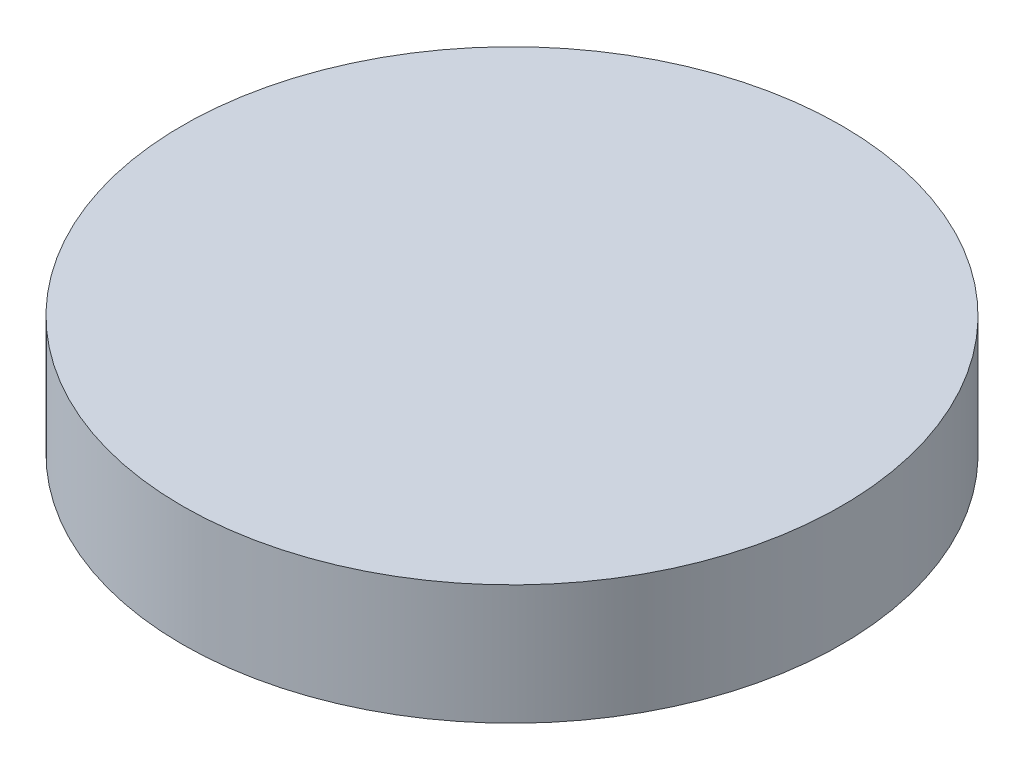
SolidWorks part; units mm, degrees
ref_plane "Front Plane" through (0, 0, 0) normal (0, 0, 1) x (1, 0, 0)
ref_plane "Top Plane" through (0, 0, 0) normal (0, 1, 0) x (1, 0, 0)
ref_plane "Right Plane" through (0, 0, 0) normal (1, 0, 0) x (0, 0, -1)
sketch "Sketch1" plane through (0, 0, 0) normal (0, 1, 0) x (1, 0, 0)
  circle A0 centre (0, 0) radius 34.925
  circle A1 centre (0, 0) radius 16.764
  dimension "D1" = 69.85
  dimension "D2" = 33.528
extrude "Boss-Extrude1" add sketch "Sketch1" along normal blind 12.7 contours A0 A1 | A1 region at (-33.9372, 0, 0) region at (0, 0, 0)
extrude "Cut-Extrude1" cut sketch "Sketch1<3>" along normal blind 6.096 contours A1 region at (0, 0, 0)
sketch "Sketch1<3>" plane through (0, 0, 0) normal (0, 1, 0) x (1, 0, 0) same geometry as "Sketch1"
